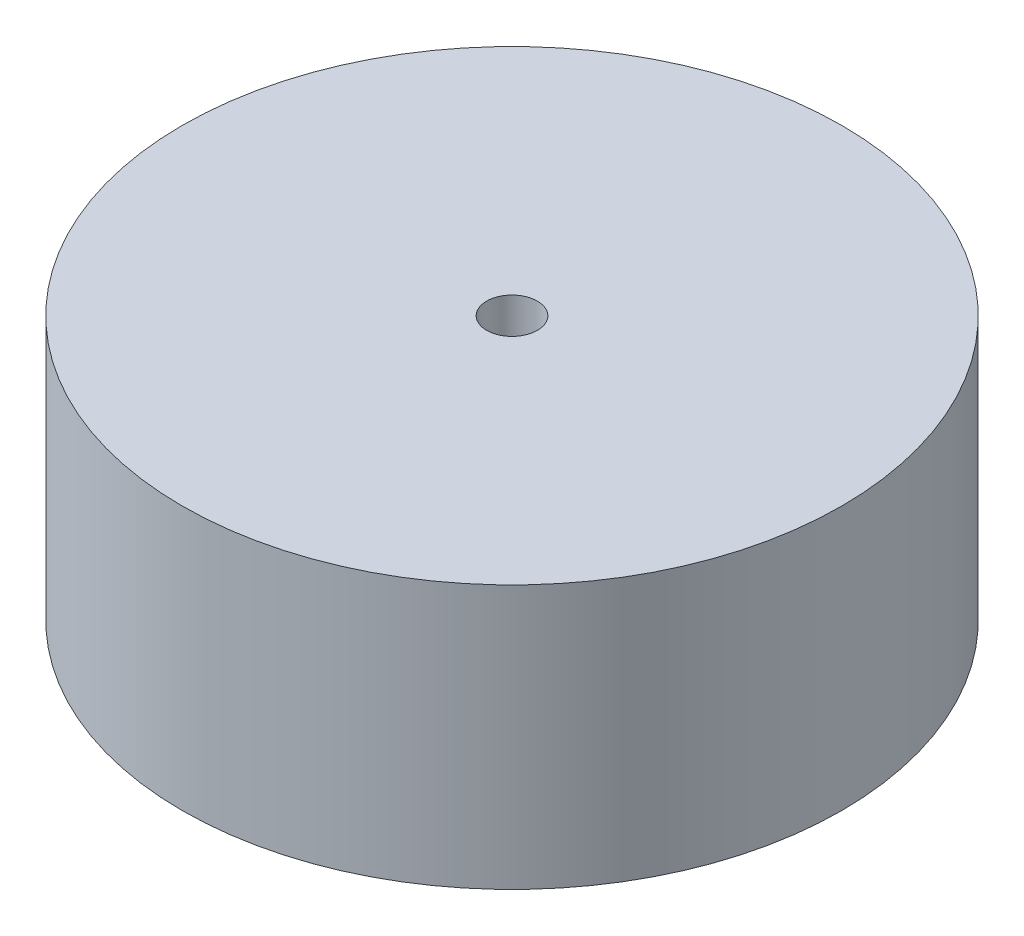
SolidWorks part; units mm, degrees
ref_plane "Front Plane" through (0, 0, 0) normal (0, 0, 1) x (1, 0, 0)
ref_plane "Top Plane" through (0, 0, 0) normal (0, 1, 0) x (1, 0, 0)
ref_plane "Right Plane" through (0, 0, 0) normal (1, 0, 0) x (0, 0, -1)
sketch "Sketch1" plane through (0, 0, 0) normal (0, 1, 0) x (1, 0, 0)
  circle A0 centre (-29.7253, 4.3466) radius 32.5
  dimension "D1" = 65
extrude "Boss-Extrude1" add sketch "Sketch1" along normal blind 26 contours A0
sketch "Sketch3" plane through (0, 0, 0) normal (0, -1, 0) x (1, 0, 0)
  circle A0 centre (-29.7253, -4.3466) radius 2.5
  dimension "D1" = 5
extrude "Cut-Extrude1" cut sketch "Sketch3" against normal through all
